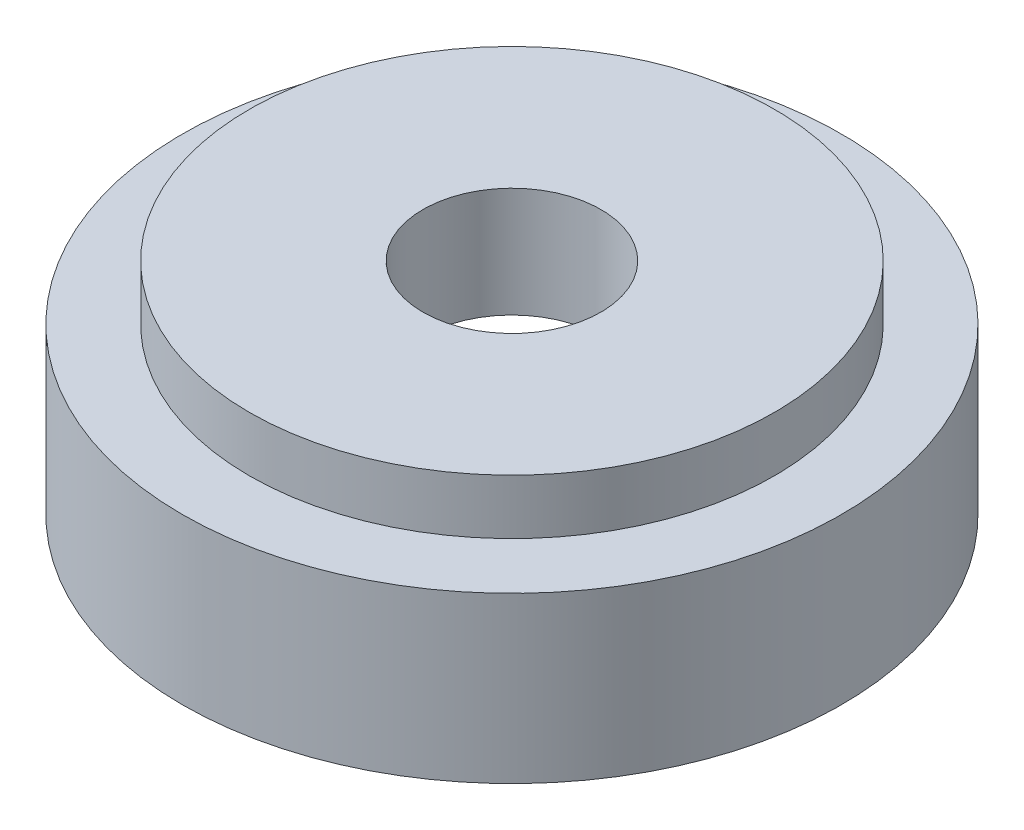
SolidWorks part; units mm, degrees
ref_plane "Front Plane" through (0, 0, 0) normal (0, 0, 1) x (1, 0, 0)
ref_plane "Top Plane" through (0, 0, 0) normal (0, 1, 0) x (1, 0, 0)
ref_plane "Right Plane" through (0, 0, 0) normal (1, 0, 0) x (0, 0, -1)
sketch "Croquis1" plane through (0, 0, 0) normal (0, 1, 0) x (1, 0, 0)
  circle A0 centre (0, 0) radius 23.9
  circle A1 centre (0, 0) radius 30
  circle A2 centre (0, 0) radius 8.1
  dimension "D1" = 47.8
  dimension "D2" = 60
  dimension "D3" = 16.2
extrude "Saliente-Extruir1" add sketch "Croquis1" along normal blind 5 contours A0 A2 region at (-23.224, 0, 0)
extrude "Saliente-Extruir2" add sketch "Croquis1<3>" against normal blind 5 contours A1 A0 | A0 A2 region at (-23.224, 0, 0) region at (-29.1515, 0, 0)
sketch "Croquis1<3>" plane through (0, 0, 0) normal (0, 1, 0) x (1, 0, 0) same geometry as "Croquis1"
extrude "Saliente-Extruir3" add sketch "Croquis1<4>" against normal blind 15 contours A1 A0 region at (-29.1515, 0, 0)
sketch "Croquis1<4>" plane through (0, 0, 0) normal (0, 1, 0) x (1, 0, 0) same geometry as "Croquis1"
equation "\"ID\" = 47.8"
equation "\"D1@Croquis1\"=\"ID\""
equation "\"OD\"=60"
equation "\"D2@Croquis1\"=\"OD\""
equation "\"Dmandril\"= 16.2"
equation "\"D3@Croquis1\"=\"Dmandril\""
